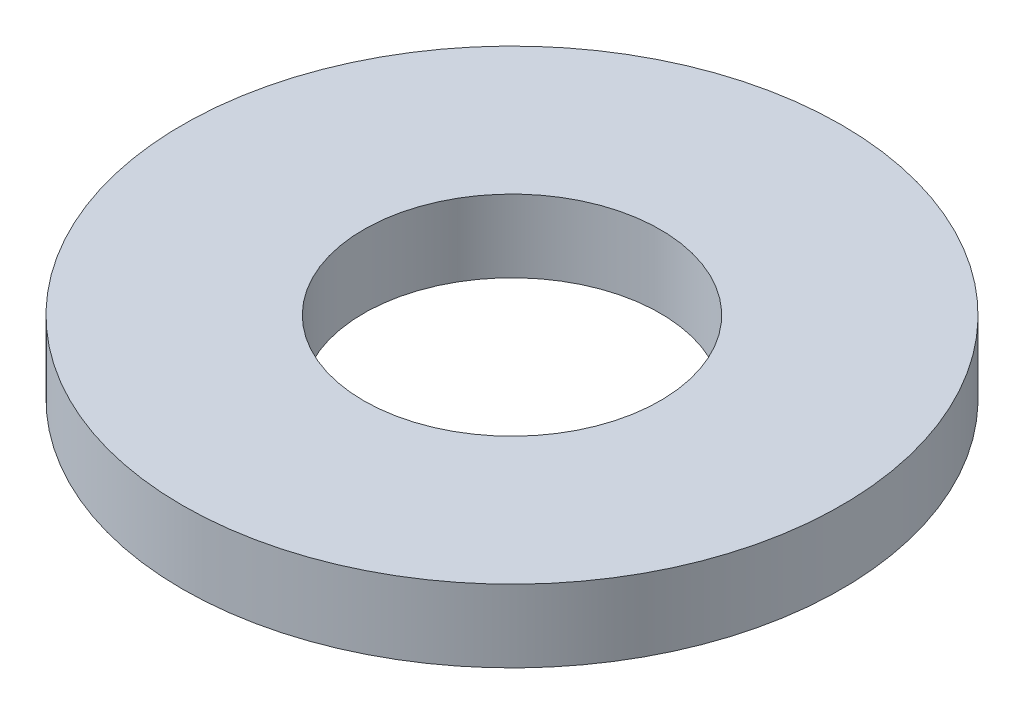
SolidWorks part; units mm, degrees
ref_plane "Front Plane" through (0, 0, 0) normal (0, 0, 1) x (1, 0, 0)
ref_plane "Top Plane" through (0, 0, 0) normal (0, 1, 0) x (1, 0, 0)
ref_plane "Right Plane" through (0, 0, 0) normal (1, 0, 0) x (0, 0, -1)
sketch "Sketch1" plane through (0, 0, 0) normal (0, 1, 0) x (1, 0, 0)
  circle A0 centre (0, 0) radius 100
  dimension "FLANGE_OD" = 200
extrude "Boss-Extrude1" add sketch "Sketch1" along normal blind 22
sketch "Sketch2" plane through (0, 0, 0) normal (0, 1, 0) x (1, 0, 0)
  circle A0 centre (0, 0) radius 45
  dimension "BORE_D" = 90
extrude "Cut-Extrude1" cut sketch "Sketch2" along normal through all
sketch "Sketch3" plane through (0, 22, 0) normal (0, 1, 0) x (1, 0, 0)
  circle A0 centre (0, 0) radius 39.1868 construction
  circle A1 centre (-39.1868, 0) radius 4.6183
  dimension "BOLT_D" = 9.2366
  dimension "BOLT_PCD" = 78.3736
extrude "Cut-Extrude2" cut sketch "Sketch3" against normal blind 16.2508 rebuild error yes
pattern_circular "CirPattern1" count 8 over 360 rebuild error yes
